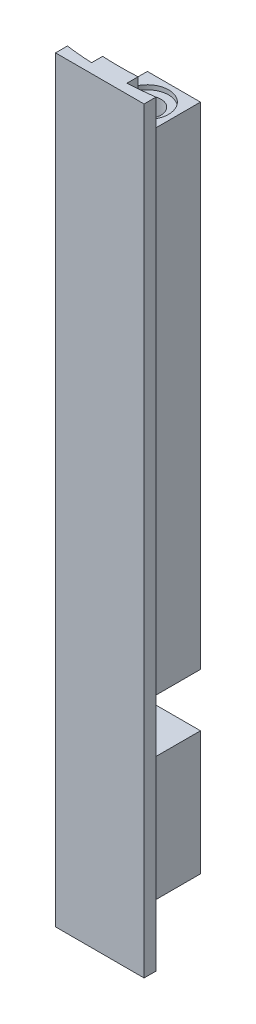
SolidWorks part; units mm, degrees
ref_plane "Front Plane" through (0, 0, 0) normal (0, 0, 1) x (1, 0, 0)
ref_plane "Top Plane" through (0, 0, 0) normal (0, 1, 0) x (1, 0, 0)
ref_plane "Right Plane" through (0, 0, 0) normal (1, 0, 0) x (0, 0, -1)
ref_plane "Plane7" through (0, -5, 0) normal (0, -1, 0) x (-1, 0, 0)
sketch "Sketch1" plane through (0, 0, 0) normal (0, 1, 0) x (1, 0, 0)
  circle A0 centre (0, 0) radius 37.5 construction
  dimension "D1" = 75
sketch "Sketch3" plane through (0, -5, 0) normal (0, -1, 0) x (1, 0, 0)
  line L0 (-3, 37.3798) -> (-3, 31.3798)
  line L1 (-3, 31.3798) -> (3, 31.3798)
  line L2 (3, 31.3798) -> (3, 37.3798)
  line L9 (0, 40.3758) -> (0, -39.6162) construction
  line L10 (0, -55) -> (0, 55) construction
  arc A0 (3, 37.3798) -> (-3, 37.3798) centre (0, 0) ccw
  circle A4 centre (0, 0) radius 37.5 construction
  dimension "D2" = 6
  dimension "D3" = 6
extrude "Boss-Extrude2" add sketch "Sketch3" along normal blind 75.5
sketch "Sketch5" plane through (0, 0, 0) normal (0, 1, 0) x (1, 0, 0)
  line L0 (-5, -38.4094) -> (-5, -39.2364)
  line L1 (5, -38.4094) -> (5, -39.4143)
  line L2 (2, -38.6818) -> (2, -37.4318)
  line L3 (-2, -38.6818) -> (-2, -37.4318)
  line L12 (0, 40.7328) -> (0, -41.0085) construction
  line L13 (0, -4.5877) -> (0, 4.5877) construction
  line L14 (0, -39.7511) -> (-5, -39.7511)
  line L15 (-5, -39.7511) -> (-5, -39.2364)
  line L16 (0, -39.7511) -> (5, -39.7511)
  line L17 (5, -39.7511) -> (5, -39.4143)
  arc A1 (-2, -37.4318) -> (2, -37.4318) centre (0, 0) ccw
  arc A2 (5, -38.4094) -> (2, -38.6818) centre (0, 0) cw
  arc A3 (-5, -38.4094) -> (-2, -38.6818) centre (0, 0) ccw
  circle A13 centre (0, 0) radius 37.5 construction
  dimension "D1" = 4
  dimension "D2" = 10
  dimension "D3" = 1.25
  dimension "D4" = 1.0049
  dimension "D5" = 1.0693
extrude "Boss-Extrude3" add sketch "Sketch5" against normal blind 85.5
sketch "Sketch7" plane through (0, 0, 0) normal (1, 0, 0) x (0, 0, -1)
  line L0 (0, 5.5) -> (0, -5.5) construction
  line L1 (0, -60.5) -> (-37.5, -60.5)
  line L2 (0, -60.5) -> (0, -66.5)
  line L3 (0, -66.5) -> (-37.5, -66.5)
  line L4 (-37.5, -60.5) -> (-37.5, -66.5)
  line L6 (-31.3798, -80.5) -> (-37.3798, -80.5) construction
  line L7 (0, -27.0167) -> (0, -72.0117) construction
  dimension "D1" = 37.5
  dimension "D2" = 6
  dimension "D3" = 14
revolve "Cut-Revolve1" cut sketch "Sketch7" angle 360 about L7
ref_plane "Plane5" through (0, -80.5, 0) normal (0, -1, 0) x (-1, 0, 0)
sketch "Sketch9" plane through (0, -80.5, 0) normal (0, -1, 0) x (-1, 0, 0)
  line L0 (0, -31.1751) -> (0, -37.6667) construction
  line L1 (0, 4.6042) -> (0, -4.6042) construction
  line L2 (-3.1738, -34.4209) -> (3.1592, -34.4209) construction
  circle A0 centre (0, -34.4209) radius 1.55
  dimension "D2" = 3.1
extrude "Cut-Extrude4" cut sketch "Sketch9" against normal blind 4.3
sketch "Sketch10" plane through (0, -80.5, 0) normal (0, -1, 0) x (-1, 0, 0)
  line L0 (0, -31.1751) -> (0, -37.6667) construction
  line L2 (-3.1738, -34.4209) -> (3.1592, -34.4209) construction
  circle A0 centre (0, -34.4209) radius 2.4
  dimension "D2" = 4.8
extrude "Cut-Extrude5" cut sketch "Sketch10" against normal blind 0.5
sketch "Sketch12" plane through (0, -5, 0) normal (0, -1, 0) x (-1, 0, 0)
  circle A0 centre (0, 0) radius 37.5 construction
sketch "Sketch13" plane through (0, -5, 0) normal (0, -1, 0) x (-1, 0, 0)
  line L0 (0, -31.134) -> (0, -37.6256) construction
  line L1 (-2.6479, -34.3798) -> (2.8747, -34.3798) construction
  line L2 (3, -37.3798) -> (3, -31.3798) construction
  line L3 (-3, -31.3798) -> (-3, -37.3798) construction
  circle A0 centre (0, -34.3798) radius 2.4
sketch "Sketch14" plane through (0, -5, 0) normal (0, -1, 0) x (-1, 0, 0)
  line L0 (0, -31.134) -> (0, -37.6256) construction
  line L2 (-3.1738, -34.3798) -> (3.1592, -34.3798) construction
  line L3 (3, -37.3798) -> (3, -31.3798) construction
  line L4 (-3, -31.3798) -> (-3, -37.3798) construction
  circle A0 centre (0, -34.3798) radius 1.55
  dimension "D2" = 3.1
extrude "Cut-Extrude6" cut sketch "Sketch13" along normal blind 0.5
extrude "Cut-Extrude7" cut sketch "Sketch14" along normal blind 4.3
